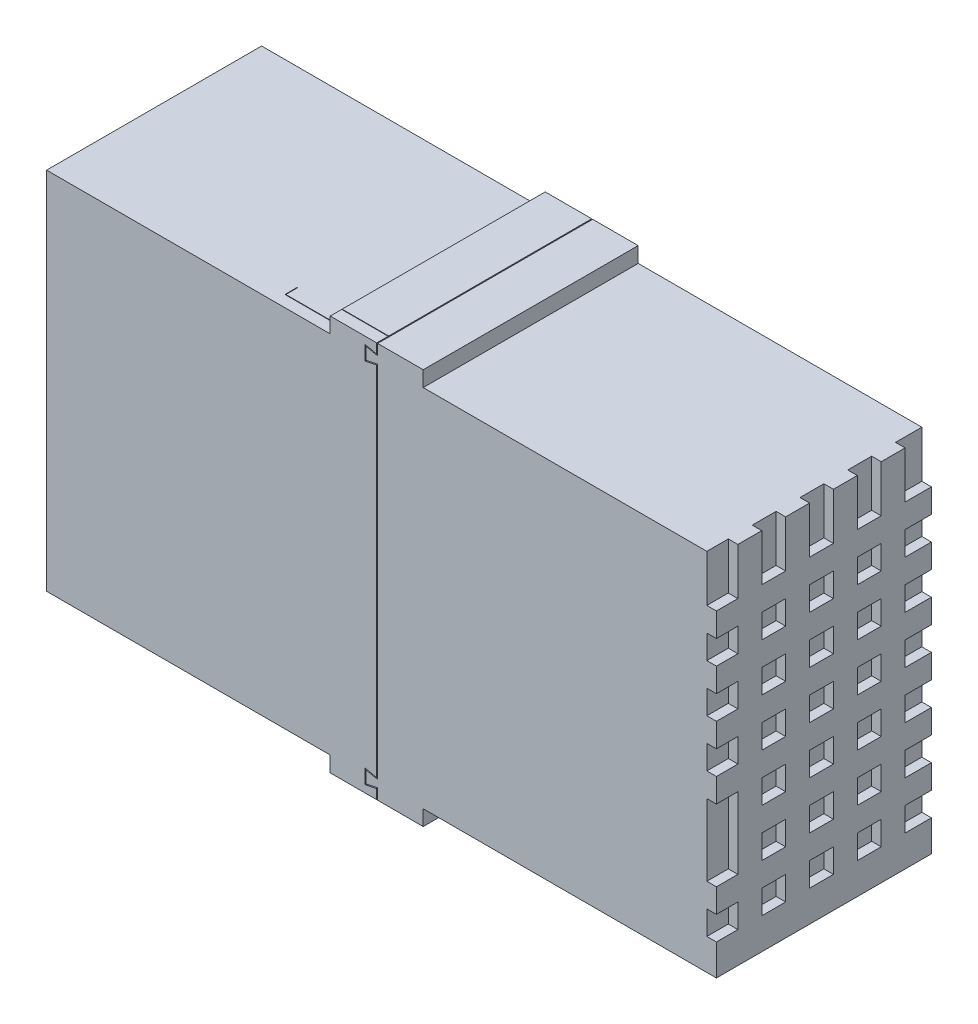
SolidWorks part; units mm, degrees
ref_plane "Front Plane" through (0, 0, 0) normal (0, 0, 1) x (1, 0, 0)
ref_plane "Top Plane" through (0, 0, 0) normal (0, 1, 0) x (1, 0, 0)
ref_plane "Right Plane" through (0, 0, 0) normal (1, 0, 0) x (0, 0, -1)
sketch "Sketch1" plane through (0, 0, 0) normal (0, 0, 1) x (1, 0, 0)
  line L1 (62.9551, -34.7601) -> (-62.9551, -34.7601)
  line L2 (62.9551, -34.7601) -> (62.9551, 34.7601)
  line L3 (62.9551, 34.7601) -> (-62.9551, 34.7601)
  line L4 (-62.9551, -34.7601) -> (-62.9551, 34.7601)
  line L5 (62.9551, -34.7601) -> (-62.9551, 34.7601) construction
  line L6 (62.9551, 34.7601) -> (-62.9551, -34.7601) construction
  line L7 (69.0947, -38.171) -> (-69.0947, -38.171)
  line L8 (69.0947, -38.171) -> (69.0947, 38.171)
  line L9 (69.0947, 38.171) -> (-69.0947, 38.171)
  line L10 (-69.0947, -38.171) -> (-69.0947, 38.171)
  line L11 (69.0947, -38.171) -> (-69.0947, 38.171) construction
  line L12 (69.0947, 38.171) -> (-69.0947, -38.171) construction
  point P0 (0, 0)
  point P6 (0, 0)
extrude "Boss-Extrude1" add sketch "Sketch1" along normal blind 40
sketch "Sketch2" plane through (0, 0, 40) normal (0, 0, 1) x (1, 0, 0)
  line L4 (-69.0947, 38.171) -> (-69.0947, -38.171)
  line L5 (-69.0947, -38.171) -> (69.0947, -38.171)
  line L6 (69.0947, -38.171) -> (69.0947, 38.171)
  line L7 (69.0947, 38.171) -> (-69.0947, 38.171)
  line L8 (-69.0947, 38.171) -> (-69.0947, -38.171)
  line L9 (-69.0947, -38.171) -> (69.0947, -38.171)
  line L10 (69.0947, -38.171) -> (69.0947, 38.171)
  line L11 (69.0947, 38.171) -> (-69.0947, 38.171)
  line M9 (-69.0947, 38.171) -> (-69.0947, -38.171)
  line M10 (-69.0947, -38.171) -> (69.0947, -38.171)
  line M11 (69.0947, -38.171) -> (69.0947, 38.171)
  line M12 (69.0947, 38.171) -> (-69.0947, 38.171)
  line M13 (62.9551, -34.7601) -> (-62.9551, -34.7601)
  line M14 (-62.9551, -34.7601) -> (-62.9551, 34.7601)
  line M15 (-62.9551, 34.7601) -> (62.9551, 34.7601)
  line M16 (62.9551, 34.7601) -> (62.9551, -34.7601)
  dimension "D1" = 0
extrude "Boss-Extrude2" add sketch "Sketch2" along normal blind 5 contours M13 M16 M15 M14 | M12 M9 M10 M11 M16 M13 M14 M15 region at (0, 36.5922, 40) region at (0, 0, 40)
sketch "Sketch3" plane through (0, 0, 0) normal (0, 0, -1) x (-1, 0, 0)
  line L0 (0, 0) -> (0, 38.171) construction
  line L1 (-69.0947, 38.171) -> (69.0947, 38.171) construction
  line L2 (0, 0) -> (38.0489, 0) construction
  line L3 (9.7303, -41.4041) -> (-9.7303, -41.4041)
  line L4 (9.7303, 34.9378) -> (-9.7303, 34.9378)
  line L5 (9.7303, 34.9378) -> (9.7303, 41.4041)
  line L6 (9.7303, 41.4041) -> (-9.7303, 41.4041)
  line L7 (-9.7303, 34.9378) -> (-9.7303, 41.4041)
  line L8 (9.7303, 34.9378) -> (-9.7303, 41.4041) construction
  line L9 (9.7303, 41.4041) -> (-9.7303, 34.9378) construction
  line L10 (-9.7303, -34.9378) -> (-9.7303, -41.4041)
  line L11 (9.7303, -34.9378) -> (-9.7303, -34.9378)
  line L12 (9.7303, -34.9378) -> (9.7303, -41.4041)
  line L13 (9.7303, -41.4041) -> (-9.7303, -34.9378) construction
  line L14 (9.7303, -34.9378) -> (-9.7303, -41.4041) construction
  point P14 (0, -38.171)
extrude "Boss-Extrude3" add sketch "Sketch3" against normal up to surface (45 mm away) up to face at (0, 0, 45)
sketch "Sketch4" plane through (0, 0, 0) normal (0, 0, -1) x (-1, 0, 0)
  line L0 (0, 41.4041) -> (0, 39.3976)
  line L1 (9.7303, 41.4041) -> (-9.7303, 41.4041) construction
  line L2 (0, 39.3976) -> (2.4914, 39.8986)
  line L3 (2.4914, 39.8986) -> (2.4914, 36.8617)
  line L4 (2.4914, 36.8617) -> (0, 37.4011)
  line L5 (0, 37.4011) -> (0, 34.7601)
  line L6 (-62.9551, 34.7601) -> (62.9551, 34.7601) construction
  line L7 (0, 0) -> (47.6016, 0) construction
  line L8 (-0.2, 41.4041) -> (-0.2, 39.1534)
  line L9 (-0.2, 39.1534) -> (2.2914, 39.6544)
  line L10 (2.2914, 39.6544) -> (2.2914, 37.1096)
  line L11 (2.2914, 37.1096) -> (-0.2, 37.649)
  line L12 (-0.2, 37.649) -> (-0.2, 34.7601)
  line L13 (-0.2, 41.4041) -> (0, 41.4041)
  line L14 (0, 34.7601) -> (-0.2, 34.7601)
  line L15 (0, -34.7601) -> (-0.2, -34.7601)
  line L16 (-0.2, -41.4041) -> (0, -41.4041)
  line L17 (-0.2, -37.649) -> (-0.2, -34.7601)
  line L18 (2.2914, -37.1096) -> (-0.2, -37.649)
  line L19 (2.2914, -39.6544) -> (2.2914, -37.1096)
  line L20 (-0.2, -39.1534) -> (2.2914, -39.6544)
  line L21 (-0.2, -41.4041) -> (-0.2, -39.1534)
  line L22 (0, -37.4011) -> (0, -34.7601)
  line L23 (2.4914, -36.8617) -> (0, -37.4011)
  line L24 (2.4914, -39.8986) -> (2.4914, -36.8617)
  line L25 (0, -39.3976) -> (2.4914, -39.8986)
  line L26 (0, -41.4041) -> (0, -39.3976)
  line M5 (-9.7303, -41.4041) -> (9.7303, -41.4041)
  line M11 (9.7303, 41.4041) -> (-9.7303, 41.4041)
  line M16 (62.9551, -34.7601) -> (-62.9551, -34.7601)
  line M18 (-62.9551, 34.7601) -> (62.9551, 34.7601)
  dimension "D1" = 0.2
extrude "Cut-Extrude1" cut sketch "Sketch4" against normal through all both and the other way through all contours L11 L12 L5 L4 L3 L2 L0 L8 L9 L10 M18 M11 | L26 L25 L24 L23 L22 L17 L18 L19 L20 L21 M5 M16 region at (0.0717, 40.4009, 0) region at (0.0717, -36.0806, 0)
sketch "Sketch5" plane through (0, 41.4041, 0) normal (0, 1, 0) x (1, 0, 0)
  line L1 (0, -42.5) -> (0, -42.6)
  line L2 (-21.5153, -42.5) -> (0, -42.5)
  line L3 (-21.6153, -42.6) -> (0, -42.6)
  line L4 (-9.7303, -45) -> (0, -45)
  line L5 (0, -45) -> (0, 0)
  line L6 (0, 0) -> (-9.7303, 0)
  line L7 (-9.7303, 0) -> (-9.7303, -45)
  line L8 (-9.7303, -45) -> (0, -45)
  line L9 (0, -45) -> (0, 0)
  line L10 (0, 0) -> (-9.7303, 0)
  line L11 (-9.7303, 0) -> (-9.7303, -45)
  line L12 (-21.6153, -42.5) -> (-21.6153, -42.6)
  line L13 (-62.9551, -42.5) -> (0, -42.5) construction
  line L14 (-62.9551, -42.6) -> (0, -42.6) construction
  line L15 (-62.9551, -40) -> (0, -40) construction
  line L16 (-21.6153, -40) -> (-21.5153, -40)
  line L17 (-21.6153, -42.5) -> (-21.6153, -40)
  line L18 (-21.5153, -42.5) -> (-21.5153, -40)
  line L19 (-21.5153, -42.5) -> (-21.5153, -39.5252) construction
  line L20 (-9.7303, -40) -> (0, -40)
  line L21 (-21.6153, -42.5) -> (-21.6153, -39.5252) construction
  line M8 (0, -45) -> (0, 0)
  line M10 (-9.7303, 0) -> (-9.7303, -45)
  dimension "D1" = 0
  dimension "D2" = 0.1
  dimension "D3" = 0.1
extrude "Cut-Extrude2" cut sketch "Sketch5" against normal through all both contours L3 L2 M10 M8 | L2 L18 L16 L17 L12 L3 M10 region at (-4.8652, 41.4041, 42.55) region at (-9.852, 41.4041, 42.55)
sketch "Sketch6" plane through (0, 0, 40) normal (0, 0, -1) x (-1, 0, 0)
  line L0 (21.4153, 34.6601) -> (0, 34.6601)
  line L6 (0, -34.6601) -> (21.4153, -34.6601)
  line L7 (21.4153, -34.6601) -> (21.4153, 34.6601)
  line L8 (0, -34.7601) -> (21.5153, -34.7601)
  line L9 (21.5153, -34.7601) -> (21.5153, 34.7601)
  line L10 (21.5153, 34.7601) -> (0, 34.7601)
  line L11 (0, 34.7601) -> (-0.2, 34.7601)
  line L12 (-0.2, 34.7601) -> (-62.9551, 34.7601)
  line L13 (-62.9551, 34.7601) -> (-62.9551, -34.7601)
  line L14 (-62.9551, -34.7601) -> (-0.2, -34.7601)
  line L15 (-0.2, -34.7601) -> (0, -34.7601)
  line L16 (0, -34.7601) -> (21.5153, -34.7601)
  line L18 (21.5153, 34.7601) -> (0, 34.7601)
  line L24 (0, 34.7601) -> (0, 34.6601)
  line L25 (0, -34.6601) -> (0, -34.7601)
  line L27 (-0.2, 34.7601) -> (-62.9551, 34.7601) construction
  line L28 (-0.2, 34.6601) -> (-62.8551, 34.6601) construction
  line L29 (-62.8551, -34.6601) -> (-0.2, -34.6601) construction
  line L30 (-62.9551, -34.7601) -> (-0.2, -34.7601) construction
  line L31 (-62.9551, 34.7601) -> (-62.9551, -34.7601) construction
  line L32 (-62.8551, 34.6601) -> (-62.8551, -34.6601) construction
  line L40 (-0.2, -34.7601) -> (0, -34.7601) construction
  line L41 (-0.2, -34.6601) -> (0, -34.6601) construction
  line L42 (0, 34.6601) -> (-0.2, 34.6601) construction
  line L43 (0, 34.7601) -> (-0.2, 34.7601) construction
  line L44 (21.5153, -34.7601) -> (21.5153, 34.7601) construction
  line L46 (21.5153, -34.7601) -> (21.5153, 34.7601)
  dimension "D1" = 0
  dimension "D2" = 0.1
sketch "Sketch7" plane through (0, 0, 40) normal (0, 0, -1) x (-1, 0, 0)
  line L0 (-0.2, 34.7601) -> (-0.2, -34.7601)
  line L8 (0, -34.7601) -> (21.5153, -34.7601)
  line L9 (21.5153, -34.7601) -> (21.5153, 34.7601)
  line L10 (21.5153, 34.7601) -> (0, 34.7601)
  line L11 (0, 34.7601) -> (-0.2, 34.7601)
  line L12 (-0.2, 34.7601) -> (-62.9551, 34.7601)
  line L13 (-62.9551, 34.7601) -> (-62.9551, -34.7601)
  line L14 (-62.9551, -34.7601) -> (-0.2, -34.7601)
  line L15 (-0.2, -34.7601) -> (0, -34.7601)
  line L16 (0, -34.7601) -> (21.5153, -34.7601)
  line L18 (21.5153, 34.7601) -> (0, 34.7601)
  line L19 (0, 34.7601) -> (-0.2, 34.7601)
  line L23 (-0.2, -34.7601) -> (0, -34.7601)
  line L26 (21.5153, -34.7601) -> (21.5153, 34.7601)
  dimension "D1" = 0
extrude "Cut-Extrude9" cut sketch "Sketch7" against normal through all both
sketch "Sketch8" plane through (-21.5153, 0, 0) normal (1, 0, 0) x (0, 0, -1)
  line L4 (-42.6, 34.7601) -> (-45, 34.7601)
  line L5 (-45, 34.7601) -> (-45, -34.7601)
  line L6 (-45, -34.7601) -> (-42.6, -34.7601)
  line L7 (-42.6, -34.7601) -> (-42.6, 34.7601)
  line L8 (-42.6, 34.7601) -> (-45, 34.7601)
  line L9 (-45, 34.7601) -> (-45, -34.7601)
  line L10 (-45, -34.7601) -> (-42.6, -34.7601)
  line L13 (-42.6, -34.7601) -> (-42.6, 34.7601)
  dimension "D1" = 0
extrude "Boss-Extrude4" add sketch "Sketch8" along normal up to surface (21.5153 mm away) separate body up to face at (0, 36.0806, 43.8)
sketch "Sketch9" plane through (0.2, 0, 0) normal (-1, 0, 0) x (0, 0, 1)
  line L2 (40, 34.7601) -> (42.5, 34.7601)
  line L3 (40, -34.7601) -> (42.5, -34.7601)
  line L4 (42.5, -34.7601) -> (42.5, 34.7601)
  line L8 (0, -34.7601) -> (0, -37.649)
  line L9 (0, -37.649) -> (45, -37.649)
  line L10 (45, -37.649) -> (45, 37.649)
  line L11 (45, 37.649) -> (0, 37.649)
  line L12 (0, 37.649) -> (0, 34.7601)
  line L15 (40, -34.7601) -> (0, -34.7601)
  line L16 (0, -34.7601) -> (0, -37.649)
  line L28 (0, 34.7601) -> (40, 34.7601)
  line L29 (40, 34.7601) -> (40, -34.7601)
  line L30 (40, 34.7601) -> (40, -34.7601)
  line M16 (40, 34.7601) -> (40, -34.7601)
  dimension "D1" = 0
extrude "Boss-Extrude5" add sketch "Sketch9" along normal blind 21.5 separate body contours L3 L4 L2 M16 region at (0.2, 0, 41.25)
combine bodies "Combine1" operation type add bodies to combine 107 108
combine bodies "Combine2" operation type add bodies to combine 109 106
sketch "Sketch10" plane through (69.0947, 0, 0) normal (1, 0, 0) x (0, 0, -1)
  line L0 (-45, 28.3614) -> (-40.5056, 28.3614)
  line L1 (-45, 23.3614) -> (-40.5056, 23.3614)
  line L2 (-45, 18.3614) -> (-40.5056, 18.3614)
  line L3 (-45, 13.3614) -> (-40.5056, 13.3614)
  line L4 (0, -38.171) -> (0, 38.171)
  line L5 (0, 38.171) -> (-45, 38.171)
  line L6 (-45, 38.171) -> (-45, -38.171)
  line L7 (-45, -38.171) -> (0, -38.171)
  line L8 (0, -38.171) -> (0, -6.6386)
  line L9 (0, 38.171) -> (-45, 38.171)
  line L10 (-45, 38.171) -> (-45, 28.3614)
  line L11 (-45, -38.171) -> (-40.5056, -38.171)
  line L12 (-45, 8.3614) -> (-40.5056, 8.3614)
  line L13 (-45, 3.3614) -> (-40.5056, 3.3614)
  line L14 (-45, -1.6386) -> (-40.5056, -1.6386)
  line L15 (-45, -6.6386) -> (-40.5056, -6.6386)
  line L16 (-45, -11.6386) -> (-40.5056, -11.6386)
  line L17 (-45, -16.6386) -> (-40.5056, -16.6386)
  line L18 (-45, -21.6386) -> (-40.5056, -21.6386)
  line L19 (-45, -26.6386) -> (-40.5056, -26.6386)
  line L20 (-45, -31.6386) -> (-40.5056, -31.6386)
  line L21 (-40.5056, 38.171) -> (-40.5056, 28.3614)
  line L22 (-35.5056, 38.171) -> (-35.5056, 28.3614)
  line L23 (-30.5056, 38.171) -> (-30.5056, 28.3614)
  line L24 (-25.5056, 38.171) -> (-25.5056, 28.3614)
  line L25 (-20.5056, 38.171) -> (-20.5056, 28.3614)
  line L26 (-15.5056, 38.171) -> (-15.5056, 28.3614)
  line L27 (-10.5056, 38.171) -> (-10.5056, 28.3614)
  line L28 (-5.5056, 38.171) -> (-5.5056, 28.3614)
  line L29 (-35.5056, 23.3614) -> (-30.5056, 23.3614)
  line L30 (-35.5056, 28.3614) -> (-30.5056, 28.3614)
  line L31 (-35.5056, 18.3614) -> (-30.5056, 18.3614)
  line L32 (-35.5056, 13.3614) -> (-30.5056, 13.3614)
  line L33 (-35.5056, 8.3614) -> (-30.5056, 8.3614)
  line L34 (-35.5056, 3.3614) -> (-30.5056, 3.3614)
  line L35 (-35.5056, -1.6386) -> (-30.5056, -1.6386)
  line L36 (-35.5056, -6.6386) -> (-30.5056, -6.6386)
  line L37 (-35.5056, -11.6386) -> (-30.5056, -11.6386)
  line L38 (-35.5056, -16.6386) -> (-30.5056, -16.6386)
  line L39 (-35.5056, -21.6386) -> (-30.5056, -21.6386)
  line L40 (-35.5056, -26.6386) -> (-30.5056, -26.6386)
  line L41 (-35.5056, -31.6386) -> (-30.5056, -31.6386)
  line L42 (-35.5056, -38.171) -> (0, -38.171)
  line L43 (-25.5056, 28.3614) -> (-20.5056, 28.3614)
  line L44 (-25.5056, 23.3614) -> (-20.5056, 23.3614)
  line L45 (-25.5056, 18.3614) -> (-20.5056, 18.3614)
  line L46 (-25.5056, 13.3614) -> (-20.5056, 13.3614)
  line L47 (-25.5056, 8.3614) -> (-20.5056, 8.3614)
  line L48 (-25.5056, 3.3614) -> (-20.5056, 3.3614)
  line L49 (-25.5056, -1.6386) -> (-20.5056, -1.6386)
  line L50 (-25.5056, -6.6386) -> (-20.5056, -6.6386)
  line L51 (-25.5056, -11.6386) -> (-20.5056, -11.6386)
  line L52 (-25.5056, -16.6386) -> (-20.5056, -16.6386)
  line L53 (-25.5056, -21.6386) -> (-20.5056, -21.6386)
  line L54 (-25.5056, -26.6386) -> (-20.5056, -26.6386)
  line L55 (-25.5056, -31.6386) -> (-20.5056, -31.6386)
  line L56 (-15.5056, 28.3614) -> (-10.5056, 28.3614)
  line L57 (-15.5056, 23.3614) -> (-10.5056, 23.3614)
  line L58 (-15.5056, 18.3614) -> (-10.5056, 18.3614)
  line L59 (-15.5056, 13.3614) -> (-10.5056, 13.3614)
  line L60 (-15.5056, 8.3614) -> (-10.5056, 8.3614)
  line L61 (-15.5056, 3.3614) -> (-10.5056, 3.3614)
  line L62 (-15.5056, -1.6386) -> (-10.5056, -1.6386)
  line L63 (-15.5056, -6.6386) -> (-10.5056, -6.6386)
  line L64 (-15.5056, -11.6386) -> (-10.5056, -11.6386)
  line L65 (-15.5056, -16.6386) -> (-10.5056, -16.6386)
  line L66 (-15.5056, -21.6386) -> (-10.5056, -21.6386)
  line L67 (-15.5056, -26.6386) -> (-10.5056, -26.6386)
  line L68 (-15.5056, -31.6386) -> (-10.5056, -31.6386)
  line L69 (-5.5056, 28.3614) -> (0, 28.3614)
  line L70 (-5.5056, 23.3614) -> (0, 23.3614)
  line L71 (-5.5056, 18.3614) -> (0, 18.3614)
  line L72 (-5.5056, 13.3614) -> (0, 13.3614)
  line L73 (-5.5056, 8.3614) -> (0, 8.3614)
  line L74 (-5.5056, 3.3614) -> (0, 3.3614)
  line L75 (-5.5056, -1.6386) -> (0, -1.6386)
  line L76 (-5.5056, -6.6386) -> (0, -6.6386)
  line L77 (-5.5056, -11.6386) -> (0, -11.6386)
  line L78 (-5.5056, -16.6386) -> (0, -16.6386)
  line L79 (-5.5056, -21.6386) -> (0, -21.6386)
  line L80 (-5.5056, -26.6386) -> (0, -26.6386)
  line L81 (-5.5056, -31.6386) -> (0, -31.6386)
  line L82 (-45, 23.3614) -> (-45, 18.3614)
  line L83 (-40.5056, 23.3614) -> (-40.5056, 18.3614)
  line L84 (-35.5056, 23.3614) -> (-35.5056, 18.3614)
  line L85 (-30.5056, 23.3614) -> (-30.5056, 18.3614)
  line L86 (-25.5056, 23.3614) -> (-25.5056, 18.3614)
  line L87 (-20.5056, 23.3614) -> (-20.5056, 18.3614)
  line L88 (-15.5056, 23.3614) -> (-15.5056, 18.3614)
  line L89 (-10.5056, 23.3614) -> (-10.5056, 18.3614)
  line L90 (-5.5056, 23.3614) -> (-5.5056, 18.3614)
  line L91 (0, 28.3614) -> (0, 38.171)
  line L92 (-45, 13.3614) -> (-45, 8.3614)
  line L93 (-40.5056, 13.3614) -> (-40.5056, 8.3614)
  line L94 (-35.5056, 13.3614) -> (-35.5056, 8.3614)
  line L95 (-30.5056, 13.3614) -> (-30.5056, 8.3614)
  line L96 (-25.5056, 13.3614) -> (-25.5056, 8.3614)
  line L97 (-20.5056, 13.3614) -> (-20.5056, 8.3614)
  line L98 (-15.5056, 13.3614) -> (-15.5056, 8.3614)
  line L99 (-10.5056, 13.3614) -> (-10.5056, 8.3614)
  line L100 (-5.5056, 13.3614) -> (-5.5056, 8.3614)
  line L101 (0, 18.3614) -> (0, 23.3614)
  line L102 (-45, 3.3614) -> (-45, -1.6386)
  line L103 (-40.5056, 3.3614) -> (-40.5056, -1.6386)
  line L104 (-35.5056, 3.3614) -> (-35.5056, -1.6386)
  line L105 (-30.5056, 3.3614) -> (-30.5056, -1.6386)
  line L106 (-25.5056, 3.3614) -> (-25.5056, -1.6386)
  line L107 (-20.5056, 3.3614) -> (-20.5056, -1.6386)
  line L108 (-15.5056, 3.3614) -> (-15.5056, -1.6386)
  line L109 (-10.5056, 3.3614) -> (-10.5056, -1.6386)
  line L110 (-5.5056, 3.3614) -> (-5.5056, -1.6386)
  line L111 (0, 8.3614) -> (0, 13.3614)
  line L112 (-45, -6.6386) -> (-45, -38.171)
  line L113 (-40.5056, -6.6386) -> (-40.5056, -21.6386)
  line L114 (-35.5056, -6.6386) -> (-35.5056, -11.6386)
  line L115 (-30.5056, -6.6386) -> (-30.5056, -11.6386)
  line L116 (-25.5056, -6.6386) -> (-25.5056, -11.6386)
  line L117 (-20.5056, -6.6386) -> (-20.5056, -11.6386)
  line L118 (-15.5056, -6.6386) -> (-15.5056, -11.6386)
  line L119 (-10.5056, -6.6386) -> (-10.5056, -11.6386)
  line L120 (-5.5056, -6.6386) -> (-5.5056, -11.6386)
  line L121 (0, -1.6386) -> (0, 3.3614)
  line L122 (-35.5056, -16.6386) -> (-35.5056, -21.6386)
  line L123 (-30.5056, -16.6386) -> (-30.5056, -21.6386)
  line L124 (-25.5056, -16.6386) -> (-25.5056, -21.6386)
  line L125 (-20.5056, -16.6386) -> (-20.5056, -21.6386)
  line L126 (-15.5056, -16.6386) -> (-15.5056, -21.6386)
  line L127 (-10.5056, -16.6386) -> (-10.5056, -21.6386)
  line L128 (-5.5056, -16.6386) -> (-5.5056, -21.6386)
  line L129 (-40.5056, -26.6386) -> (-40.5056, -31.6386)
  line L130 (-35.5056, -26.6386) -> (-35.5056, -31.6386)
  line L131 (-30.5056, -26.6386) -> (-30.5056, -31.6386)
  line L132 (-25.5056, -26.6386) -> (-25.5056, -31.6386)
  line L133 (-20.5056, -26.6386) -> (-20.5056, -31.6386)
  line L134 (-15.5056, -26.6386) -> (-15.5056, -31.6386)
  line L135 (-10.5056, -26.6386) -> (-10.5056, -31.6386)
  line L136 (-5.5056, -26.6386) -> (-5.5056, -31.6386)
  line L137 (-45, 28.3614) -> (-45, -26.6386)
  line L138 (0, 28.3614) -> (0, -26.6386)
  line M5 (0, -38.171) -> (0, 38.171)
  line M7 (-45, 38.171) -> (-45, -38.171)
  dimension "D1" = 0
  dimension "D2" = 13
  dimension "D3" = 8
extrude "Boss-Extrude6" add sketch "Sketch10" along normal blind 2 contours L136 L80 L8 L79 L128 L78 L77 L120 L76 L75 L110 L74 L73 L100 L72 L71 L90 L70 L69 L28 L9 L27 L56 L26 L25 L43 L24 L23 L30 L22 L21 L0 L1 L83 L2 L3 L93 L12 L13 L103 M5 M7 region at (69.0947, -1.9591, 22.4783)
ref_plane "Plane1" through (0, 0, 22.5) normal (0, 0, -1) x (-1, 0, 0)
sketch "Sketch11" plane through (0, 0, 22.5) normal (0, 0, -1) x (-1, 0, 0)
  line L0 (-9.7303, -38.171) -> (-71.0947, -38.171) construction
  line L1 (-24.1034, -38.171) -> (-54.5678, -38.171)
  line L2 (-25.1034, -39.171) -> (-53.5678, -39.171)
  line L3 (-54.5678, -38.171) -> (-24.1034, -38.171)
  line L4 (-54.5678, -38.171) -> (-54.5678, -54.3466)
  line L5 (-54.5678, -54.3466) -> (-24.1034, -54.3466)
  line L6 (-24.1034, -38.171) -> (-24.1034, -54.3466)
  line L7 (-53.5678, -39.171) -> (-53.5678, -53.3466)
  line L8 (-53.5678, -53.3466) -> (-25.1034, -53.3466)
  line L9 (-25.1034, -39.171) -> (-25.1034, -53.3466)
  line L10 (-24.1034, -39.171) -> (-54.5678, -39.171) construction
  line L11 (-53.5678, -38.171) -> (-53.5678, -53.3466) construction
  line L12 (-25.1034, -38.171) -> (-25.1034, -53.3466) construction
  dimension "D1" = 1
extrude "Boss-Extrude7" add sketch "Sketch11" along normal blind 4 and the other way blind 4 contours L6 L1 L4 L5 L2 L9 L8 L7 region at (24.4484, -46.2588, 22.5)
fillet "Fillet1" radius 3 4 edges at (25.1034, -53.3466, 22.5) (53.5678, -53.3466, 22.5) (25.1034, -39.171, 22.5) (53.5678, -39.171, 22.5)
fillet "Fillet2" radius 3 6 edges at (54.5678, -38.171, 22.5) (24.1034, -38.171, 22.5) (24.1034, -54.3466, 22.5) (54.5678, -54.3466, 22.5) (39.3356, -54.3466, 26.5) (39.3356, -54.3466, 18.5)
